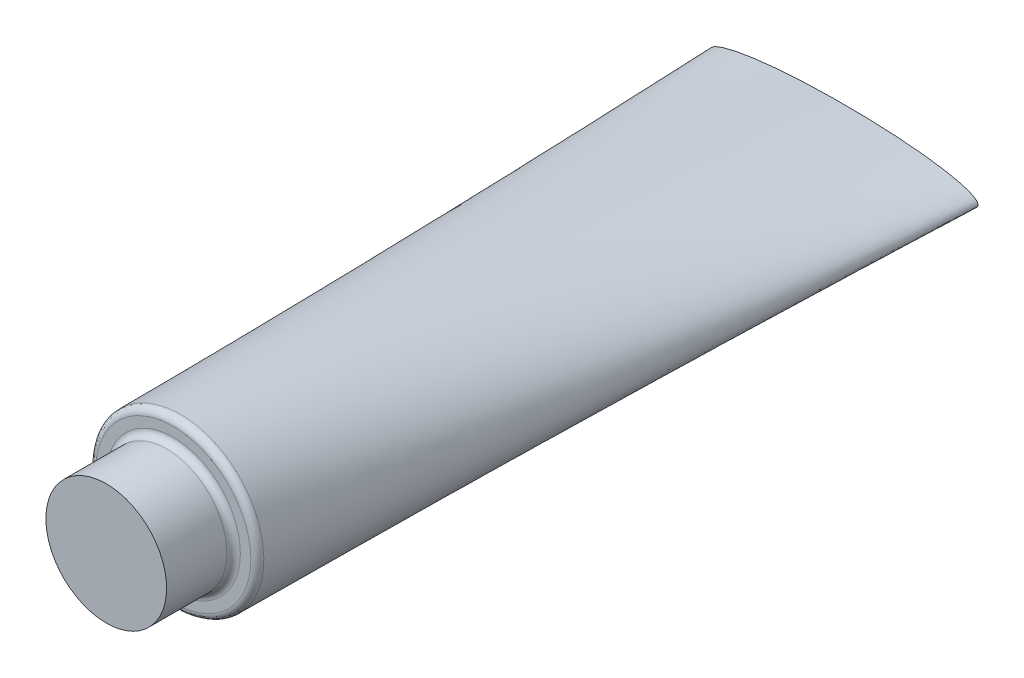
SolidWorks part; units mm, degrees
ref_plane "Ebene vorne" through (0, 0, 0) normal (0, 0, 1) x (1, 0, 0)
ref_plane "Ebene oben" through (0, 0, 0) normal (0, 1, 0) x (1, 0, 0)
ref_plane "Ebene rechts" through (0, 0, 0) normal (1, 0, 0) x (0, 0, -1)
sketch "Skizze1" plane through (0, 0, 0) normal (0, 0, 1) x (1, 0, 0)
  ellipse E0 centre (0, 0) end of major axis (-20, 0) minor radius 3
ref_plane "Ebene1" through (0, 0, 100) normal (0, 0, 1) x (1, 0, 0)
sketch "Skizze2" plane through (0, 0, 100) normal (0, 0, 1) x (1, 0, 0)
  circle A0 centre (0, 0) radius 12.5
  dimension "D1" = 25
loft "Ausformung2" add profiles "Skizze1", "Skizze2" connector at (-8.9677, 2.6815, 0) connector at (-3.5703, 11.9793, 100)
sketch "Skizze3" plane through (0, 0, 100) normal (0, 0, 1) x (1, 0, 0)
  circle A0 centre (0, 0) radius 9
extrude "Aufsatz-Linear austragen1" add sketch "Skizze3" along normal blind 10
fillet "Verrundung3" radius 1 1 edges at (9, 0, 100)
fillet "Verrundung4" radius 1 1 edges at (12.5, 0, 100)
